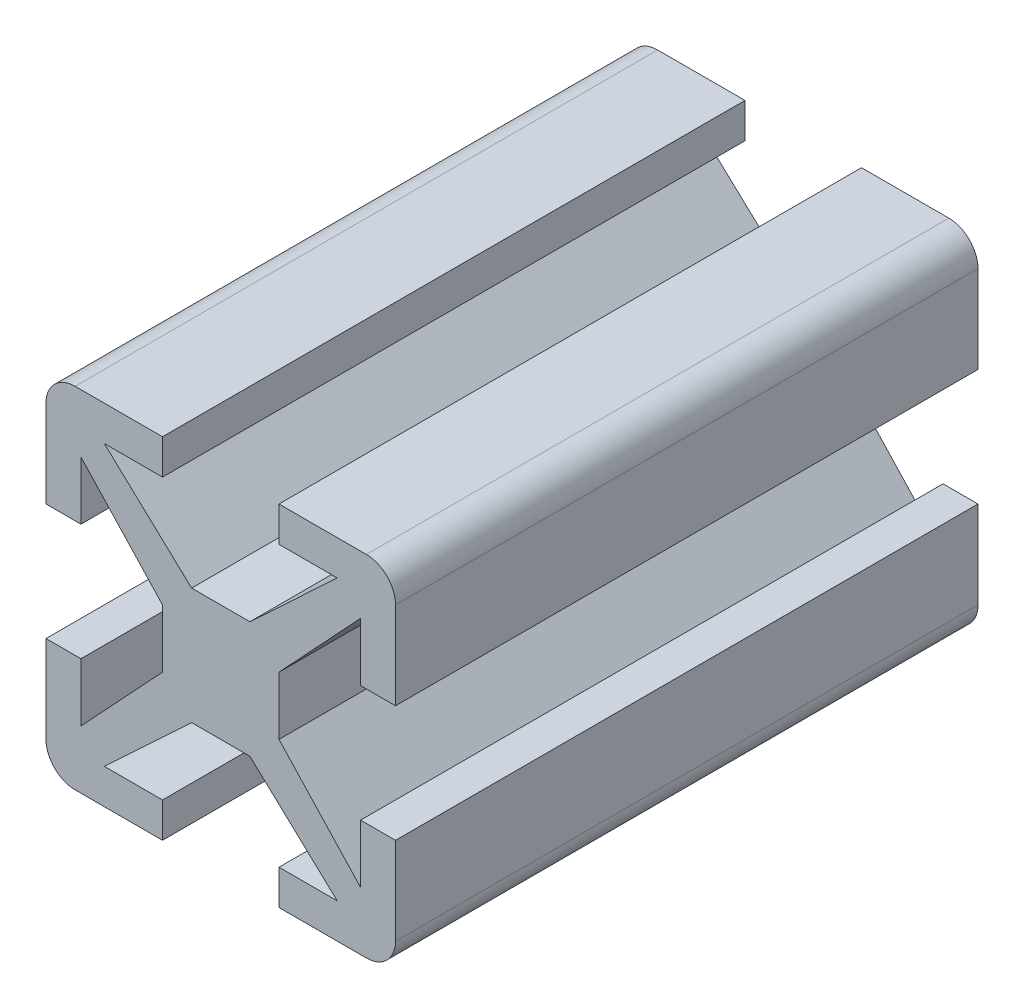
SolidWorks part; units mm, degrees
ref_plane "Plan de face" through (0, 0, 0) normal (0, 0, 1) x (1, 0, 0)
ref_plane "Plan de dessus" through (0, 0, 0) normal (0, 1, 0) x (1, 0, 0)
ref_plane "Plan de droite" through (0, 0, 0) normal (1, 0, 0) x (0, 0, -1)
sketch "Esquisse1" plane through (0, 0, 0) normal (0, 0, 1) x (1, 0, 0)
  line L0 (-6, 5) -> (-6, -5)
  line L1 (-5, 6) -> (5, 6)
  line L2 (-5, -6) -> (5, -6)
  line L3 (6, 5) -> (6, -5)
  line L4 (-5, 5) -> (5, -5) construction
  line L5 (5, 5) -> (-5, -5) construction
  arc A0 (-5, 6) -> (-6, 5) centre (-5, 5) ccw
  arc A1 (5, 6) -> (6, 5) centre (5, 5) cw
  arc A2 (6, -5) -> (5, -6) centre (5, -5) cw
  arc A3 (-5, -6) -> (-6, -5) centre (-5, -5) cw
  point P12 (0, 0)
  dimension "D1" = 1
  dimension "D2" = 1
  dimension "D4" = 1
  dimension "D3" = 12
extrude "Extrusion1" add sketch "Esquisse1" along normal mid plane 20
sketch "Esquisse3" plane through (0, 0, 10) normal (0, 0, 1) x (1, 0, 0)
  line L0 (6, 2) -> (4.8, 2)
  line L2 (4.8, 2) -> (4.8, 4)
  line L3 (2, 1) -> (2, -1)
  line L4 (4.8, -4) -> (4.8, -2)
  line L5 (4.8, -2) -> (6, -2)
  line L6 (6, -5) -> (6, 5) construction
  line L7 (4.8, 4) -> (2, 1)
  line L8 (6, 2) -> (6, -2)
  line L9 (4.8, -4) -> (2, -1)
  point P4 (6, 0)
  point P10 (6, 0)
  dimension "D1" = 4
  dimension "D2" = 1.2
  dimension "D3" = 4
  dimension "D4" = 2
  dimension "D5" = 2
extrude "Enlèv. mat.-Extru.1" cut sketch "Esquisse3" against normal blind 300
ref_axis "Axe1" through (0, 0, -1) along (0, 0, 1)
pattern_circular "Répétition circulaire1" count 4 every 90 about axis through (0, 0, -1) along (0, 0, 1) of "Enlèv. mat.-Extru.1"
